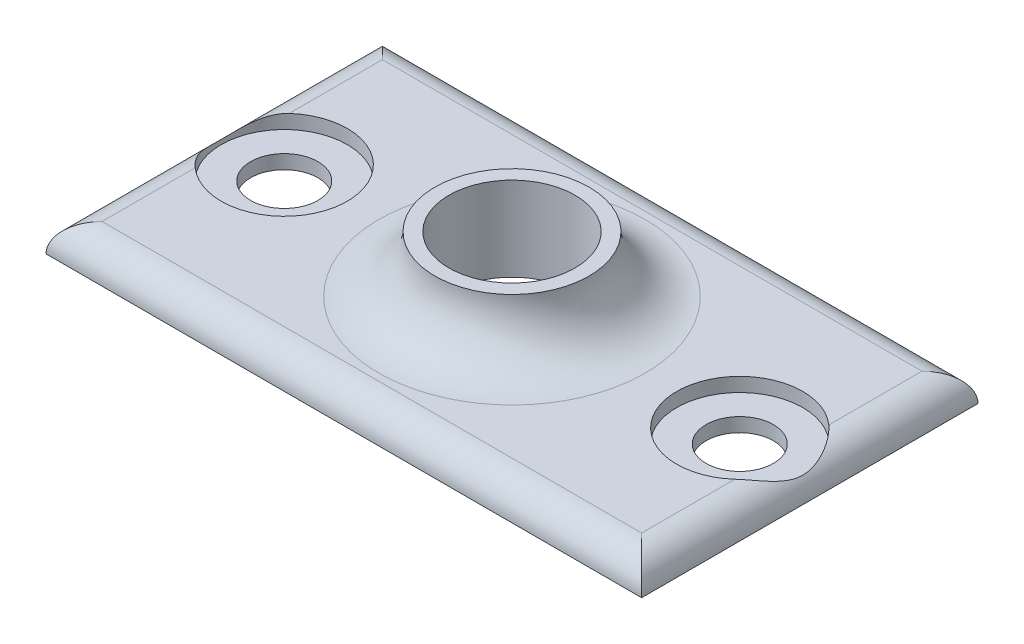
SolidWorks part; units mm, degrees
ref_plane "Front Plane" through (0, 0, 0) normal (0, 0, 1) x (1, 0, 0)
ref_plane "Top Plane" through (0, 0, 0) normal (0, 1, 0) x (1, 0, 0)
ref_plane "Right Plane" through (0, 0, 0) normal (1, 0, 0) x (0, 0, -1)
sketch "Sketch1" plane through (0, 0, 0) normal (0, 1, 0) x (1, 0, 0)
  line L0 (16.25, 0) -> (-16.25, 0) construction
  line L2 (21.25, 12) -> (-21.25, 12)
  line L3 (21.25, 12) -> (21.25, -12)
  line L4 (21.25, -12) -> (-21.25, -12)
  line L5 (-21.25, 12) -> (-21.25, -12)
  line L6 (21.25, 12) -> (-21.25, -12) construction
  line L7 (21.25, -12) -> (-21.25, 12) construction
  circle A3 centre (0, 0) radius 4.5
  circle A4 centre (16.25, 0) radius 4.5
  circle A5 centre (-16.25, 0) radius 4.5
  point P0 (0, 0)
  point P4 (0, 0)
  dimension "D2" = 24
  dimension "D4" = 9
  dimension "D5" = 9
  dimension "D1" = 32.5
  dimension "D3" = 42.5
extrude "Boss-Extrude1" add sketch "Sketch1" along normal blind 2
extrude "Boss-Extrude2" add sketch "Sketch1<2>" along normal blind 1 contours A4 | A5 region at (16.25, 0, 0) region at (-16.25, 0, 0)
sketch "Sketch1<2>" plane through (0, 0, 0) normal (0, 1, 0) x (1, 0, 0) same geometry as "Sketch1"
sketch "Sketch2" plane through (0, 0, 0) normal (0, 0, 1) x (1, 0, 0)
  line L0 (-21.25, 2) -> (21.25, 2) construction
  line L1 (-5.5, 2) -> (-4.5, 2)
  line L2 (-5.5, 2) -> (-5.5, 6)
  line L3 (-5.5, 6) -> (-4.5, 6)
  line L4 (-4.5, 2) -> (-4.5, 6)
  line L5 (0, 0) -> (0, 50000) construction
  dimension "D1" = 4.5
  dimension "D2" = 5.5
  dimension "D3" = 4
revolve "Revolve1" add sketch "Sketch2" angle 360 about L5
fillet "Fillet3" radius 2 4 edges at (0, 2, 12) (0, 2, -12) (21.25, 2, 0) (-21.25, 2, 0)
fillet "Fillet2" radius 4 1 edges at (0, 2, -5.5)
chamfer "Chamfer1" [suppressed] distance 3 angle 45
hole_wizard "M4 Clearance Hole1" positions "Sketch3" profile "Sketch4" hole size "M4" standard "ANSI Metric" end condition through all
sketch "Sketch3" plane through (0, 0, 0) normal (0, -1, 0) x (-1, 0, 0)
  point P0 (-16.25, 0)
  point P3 (16.25, 0)
sketch "Sketch4" plane through (16.25, 0, 0) normal (1, 0, 0) x (0, 0, -1)
  line L0 (0, 0) -> (0, 6)
  line L1 (0, 6) -> (2.4, 6)
  line L2 (2.4, 6) -> (2.4, 0)
  line L5 (2.4, 0) -> (0, 0)
  line L11 (0, -6.35) -> (0, 107.95) construction
  dimension "Thru Hole Dia." = 4.8
  dimension "Thru Hole Depth" = 6
